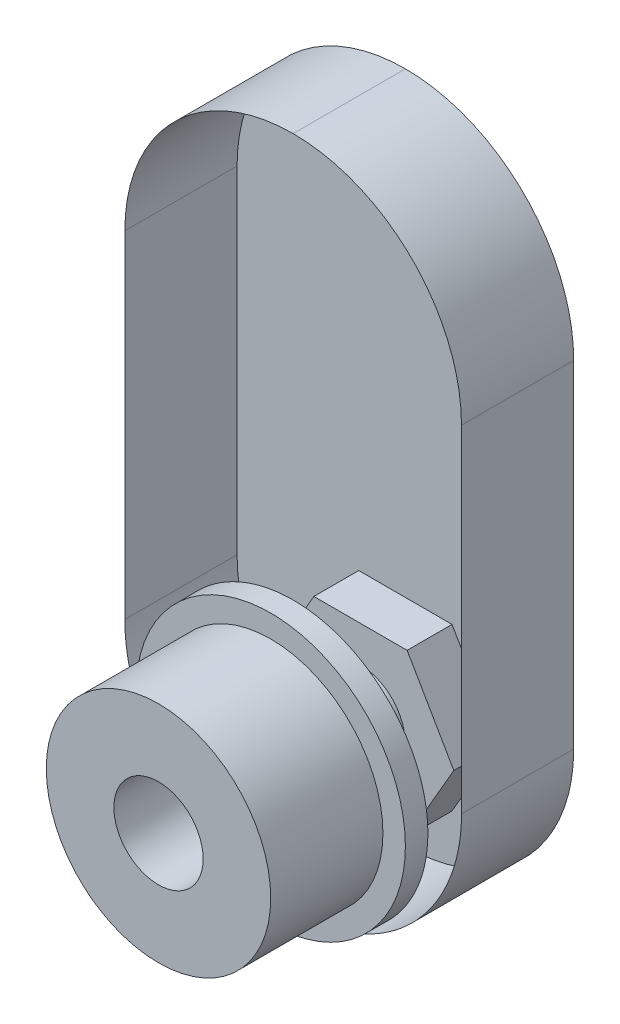
SolidWorks part; units mm, degrees
ref_plane "Front Plane" through (0, 0, 0) normal (0, 0, 1) x (1, 0, 0)
ref_plane "Top Plane" through (0, 0, 0) normal (0, 1, 0) x (1, 0, 0)
ref_plane "Right Plane" through (0, 0, 0) normal (1, 0, 0) x (0, 0, -1)
sketch "Sketch1" plane through (0, 0, 0) normal (0, 0, 1) x (1, 0, 0)
  line L1 (-9.525, 0) -> (9.525, 0)
  line L2 (-9.525, 0) -> (-9.525, 38.1)
  line L3 (-9.525, 38.1) -> (9.525, 38.1)
  line L4 (9.525, 0) -> (9.525, 38.1)
  point P4 (0, 0)
  point P5 (0, 0)
  point P6 (-5.977, 0)
  dimension "D1" = 38.1
  dimension "D2" = 19.05
extrude "Boss-Extrude1" add sketch "Sketch1" along normal blind 6.35
sketch "Sketch2" plane through (0, 0, 6.35) normal (0, 0, 1) x (1, 0, 0)
  line L3 (-9.525, 0) -> (9.525, 0) construction
  circle A0 centre (0, 7.62) radius 6.35
  point P2 (0, 0)
  point P4 (0, 0)
  dimension "D1" = 12.7
  dimension "D2" = 7.62
extrude "Boss-Extrude2" add sketch "Sketch2" along normal blind 7.62
hole_wizard "#8 (0.199) Diameter Hole1" positions "Sketch3" profile "Sketch4" hole size "#8" standard "ANSI Inch" end condition through all
sketch "Sketch3" plane through (0, 0, 13.97) normal (0, 0, 1) x (1, 0, 0)
  circle A0 centre (0, 7.62) radius 6.35 construction
  point P0 (0, 7.62)
  point P6 (0, 0)
sketch "Sketch4" plane through (0, 7.62, 13.97) normal (1, 0, 0) x (0, -1, 0)
  line L0 (0, 0) -> (0, 13.97)
  line L1 (0, 13.97) -> (2.5273, 13.97)
  line L2 (2.5273, 13.97) -> (2.5273, 0)
  line L5 (2.5273, 0) -> (0, 0)
  line L11 (0, -6.35) -> (0, 107.95) construction
  dimension "Thru Hole Dia." = 5.0546
  dimension "Thru Hole Depth" = 13.97
sketch "Sketch5" plane through (0, 0, 0) normal (0, 0, -1) x (-1, 0, 0)
  line L1 (2.6396, 3.048) -> (5.2793, 7.62)
  line L2 (5.2793, 7.62) -> (2.6396, 12.192)
  line L3 (2.6396, 12.192) -> (-2.6396, 12.192)
  line L4 (-2.6396, 12.192) -> (-5.2793, 7.62)
  line L5 (-5.2793, 7.62) -> (-2.6396, 3.048)
  line L6 (-2.6396, 3.048) -> (2.6396, 3.048)
  circle A0 centre (0, 7.62) radius 4.572 construction
  dimension "D1" = 9.144
extrude "Cut-Extrude1" cut sketch "Sketch5" against normal blind 2.54
sketch "Sketch7" plane through (0, 0, 6.35) normal (0, 0, 1) x (1, 0, 0)
  circle A0 centre (0, 7.62) radius 7.62
  circle A1 centre (0, 7.62) radius 6.35
  circle A2 centre (0, 7.62) radius 6.35 construction
  dimension "D1" = 15.24
extrude "Boss-Extrude3" add sketch "Sketch7" along normal blind 1.27
fillet "Fillet1" radius 9.525 4 edges at (9.525, 0, 3.175) (-9.525, 0, 3.175) (9.525, 38.1, 3.175) (-9.525, 38.1, 3.175)
